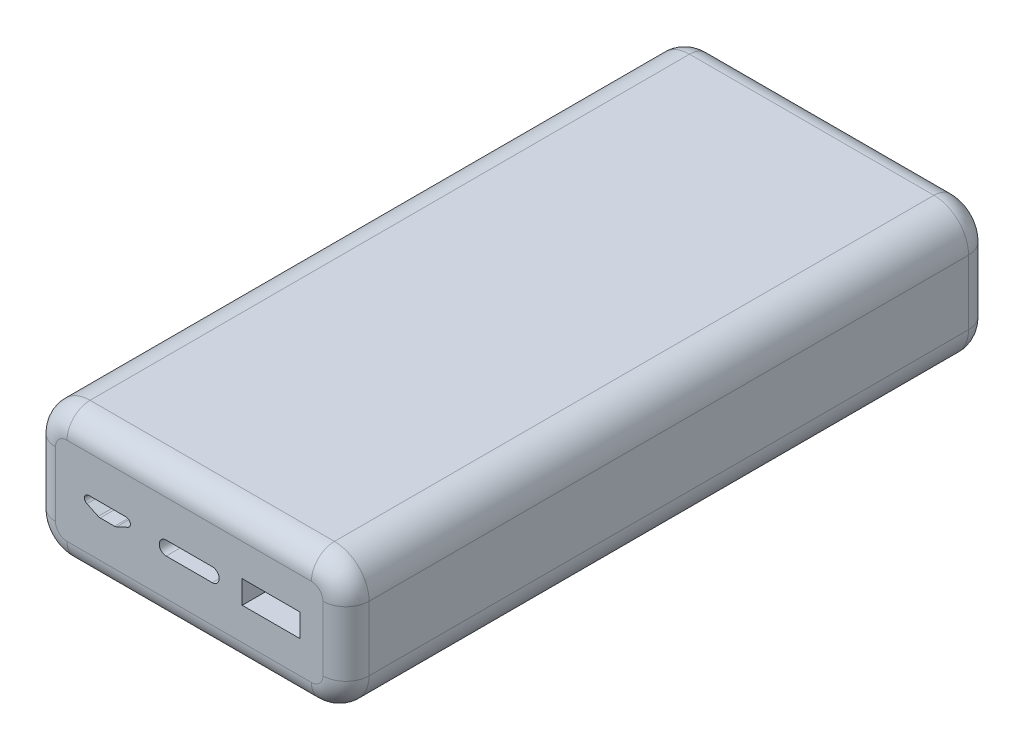
SolidWorks part; units mm, degrees
ref_plane "Plan de face" through (0, 0, 0) normal (0, 0, 1) x (1, 0, 0)
ref_plane "Plan de dessus" through (0, 0, 0) normal (0, 1, 0) x (1, 0, 0)
ref_plane "Plan de droite" through (0, 0, 0) normal (1, 0, 0) x (0, 0, -1)
sketch "Esquisse1" plane through (0, 0, 0) normal (0, 0, 1) x (1, 0, 0)
  line L1 (-34, 14.5) -> (34, 14.5)
  line L2 (-34, 14.5) -> (-34, -14.5)
  line L3 (-34, -14.5) -> (34, -14.5)
  line L4 (34, 14.5) -> (34, -14.5)
  point P4 (0, 14.5)
  point P6 (-34, 0)
  dimension "D1" = 29
  dimension "D2" = 68
extrude "Boss.-Extru.1" add sketch "Esquisse1" along normal blind 140
fillet "Congé1" radius 7.5 4 edges at (34, -14.5, 70) (34, 14.5, 70) (-34, -14.5, 70) (-34, 14.5, 70)
fillet "Congé2" radius 5 16 edges at (-31.8033, 12.3033, 0) (0, 14.5, 0) (31.8033, 12.3033, 0) (34, 0, 0) (31.8033, -12.3033, 0) (0, -14.5, 0) (-31.8033, -12.3033, 0) (-31.8033, 12.3033, 140) (0, 14.5, 140) (31.8033, 12.3033, 140) (34, 0, 140) (31.8033, -12.3033, 140) (0, -14.5, 140) (-31.8033, -12.3033, 140) (-34, 0, 0) (-34, 0, 140)
sketch "Esquisse2" plane through (0, 0, 140) normal (0, 0, 1) x (1, 0, 0)
  line L0 (5, 0) -> (-5, 0) construction
  line L1 (-22.75, 1.5) -> (-12.75, 1.5)
  line L2 (-22.75, 1.5) -> (-22.75, -1.5)
  line L3 (-22.75, -1.5) -> (-12.75, -1.5) construction
  line L4 (-12.75, 1.5) -> (-12.75, -1.5)
  line L5 (11.5, 2.5) -> (24, 2.5)
  line L6 (11.5, 2.5) -> (11.5, -2.5)
  line L7 (11.5, -2.5) -> (24, -2.5)
  line L8 (24, 2.5) -> (24, -2.5)
  line L13 (5, -1.5) -> (-5, -1.5)
  line L14 (5, 1.5) -> (-5, 1.5)
  line L15 (11.5, 0) -> (6.5, 0) construction
  line L16 (24, 0) -> (29, 0) construction
  line L17 (29, -7) -> (29, 7) construction
  line L18 (-12.75, 0) -> (-6.5, 0) construction
  line L19 (-22.75, 0) -> (-29, 0) construction
  line L20 (-29, 7) -> (-29, -7) construction
  line L21 (-22.75, 0) -> (-19.5273, -1.5)
  line L22 (-19.5273, -1.5) -> (-15.9727, -1.5)
  line L23 (-15.9727, -1.5) -> (-12.75, 0)
  arc A0 (5, -1.5) -> (5, 1.5) centre (5, 0) ccw
  arc A1 (-5, 1.5) -> (-5, -1.5) centre (-5, 0) ccw
  point P10 (0, 0)
  point P15 (-12.75, 0)
  point P16 (11.5, 0)
  dimension "D4" = 10
  dimension "D1" = 12.5
  dimension "D2" = 5
  dimension "D3" = 3
extrude "Enlèv. mat.-Extru.1" cut sketch "Esquisse2" against normal blind 5 contours L22 L23 L4 L1 L2 L21 | L14 A1 L13 A0 | L8 L5 L6 L7 region at (-17.75, 0.1921, 140) region at (17.75, 0, 140) region at (0, 0, 140)
fillet "Congé3" radius 1 6 edges at (-15.9727, -1.5, 137.5) (-19.5273, -1.5, 137.5) (-22.75, 0, 137.5) (-22.75, 1.5, 137.5) (-12.75, 1.5, 137.5) (-12.75, 0, 137.5)
